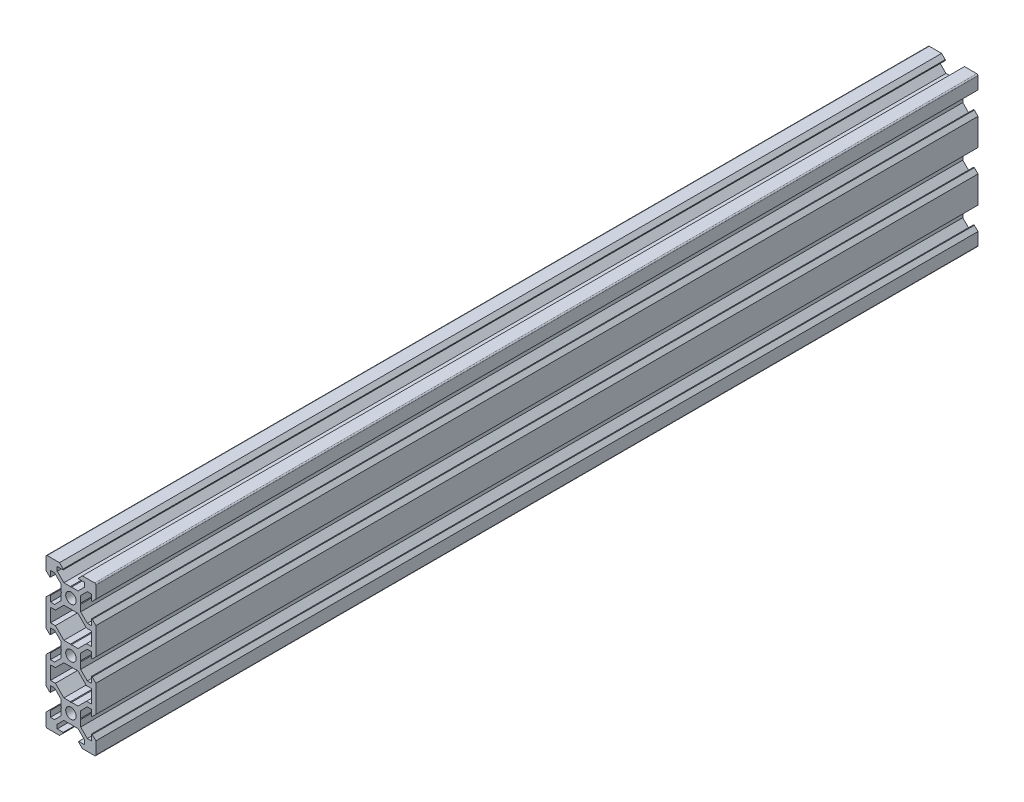
SolidWorks part; units mm, degrees
ref_plane "Plan de face" through (0, 0, 0) normal (0, 0, 1) x (1, 0, 0)
ref_plane "Plan de dessus" through (0, 0, 0) normal (0, 1, 0) x (1, 0, 0)
ref_plane "Plan de droite" through (0, 0, 0) normal (1, 0, 0) x (0, 0, -1)
ref_axis "Axe" through (0, 0, -13.782) along (0, 0, 1)
sketch "Esquisse1" plane through (0, 0, 0) normal (0, 0, 1) x (1, 0, 0)
  line L0 (0, 27.6392) -> (0, -27.6392) construction
  line L1 (-33.6074, 0) -> (33.6074, 0) construction
  line L2 (0, 0) -> (-22.2114, 22.2114) construction
  line L3 (-9.5, 10) -> (-4.58, 10)
  line L4 (-4.58, 10) -> (-3.125, 8.545)
  line L5 (-3.125, 8.545) -> (-3.125, 8.2)
  line L6 (-3.125, 8.2) -> (-5.5, 8.2)
  line L7 (-2.8393, 3.9) -> (-5.5, 6.5607)
  line L8 (-2.8393, 3.9) -> (-0.21, 3.9)
  line L9 (-5.5, 6.5607) -> (-5.5, 8.2)
  line L10 (0, 3.69) -> (0, 2.1)
  line L11 (-3.9, 2.8393) -> (-6.5607, 5.5)
  line L12 (-8.545, 3.125) -> (-8.2, 3.125)
  line L13 (-8.2, 3.125) -> (-8.2, 5.5)
  line L14 (-6.5607, 5.5) -> (-8.2, 5.5)
  line L15 (-10, 4.58) -> (-8.545, 3.125)
  line L16 (-10, 9.5) -> (-10, 4.58)
  line L17 (-0.21, 3.9) -> (0, 3.69)
  line L18 (-3.9, 2.8393) -> (-3.9, 0.21)
  line L19 (-6.2393, -12.7) -> (-8.2, -12.7)
  line L20 (-3.9, 0.21) -> (-3.69, 0)
  line L21 (-0.21, -3.9) -> (0, -3.69)
  line L22 (0, -3.69) -> (0, -2.1)
  line L23 (-6.5607, -5.5) -> (-8.2, -5.5)
  line L24 (-2.8393, -3.9) -> (-0.21, -3.9)
  line L25 (-8.545, -3.125) -> (-8.2, -3.125)
  line L26 (-10, -4.58) -> (-8.545, -3.125)
  line L27 (-8.2, -3.125) -> (-8.2, -5.5)
  line L28 (-2.8393, -3.9) -> (-6.2393, -7.3)
  line L29 (-3.9, -2.8393) -> (-6.5607, -5.5)
  line L30 (-3.9, -2.8393) -> (-3.9, -0.21)
  line L31 (-3.9, -0.21) -> (-3.69, 0)
  line L32 (-6.2393, -7.3) -> (-8.2, -7.3)
  line L33 (-8.2, -7.3) -> (-8.2, -12.7)
  line L34 (-8.2, -10) -> (-10, -10) construction
  line L35 (-10, -15.42) -> (-10, -4.58)
  line L36 (-3.9, -19.79) -> (-3.69, -20)
  line L37 (-3.9, -17.1607) -> (-3.9, -19.79)
  line L38 (-3.9, -17.1607) -> (-6.5607, -14.5)
  line L39 (-2.8393, -16.1) -> (-6.2393, -12.7)
  line L40 (-8.2, -16.875) -> (-8.2, -14.5)
  line L41 (-10, -15.42) -> (-8.545, -16.875)
  line L42 (-8.545, -16.875) -> (-8.2, -16.875)
  line L43 (-2.8393, -16.1) -> (-0.21, -16.1)
  line L44 (-6.5607, -14.5) -> (-8.2, -14.5)
  line L45 (0, -16.31) -> (0, -17.9)
  line L46 (-0.21, -16.1) -> (0, -16.31)
  line L47 (-8.2, -30) -> (-10, -30) construction
  line L48 (-3.69, -20) -> (0, -20) construction
  line L49 (-0.21, -23.9) -> (0, -23.69)
  line L50 (0, -23.69) -> (0, -22.1)
  line L51 (-6.5607, -25.5) -> (-8.2, -25.5)
  line L52 (-2.8393, -23.9) -> (-0.21, -23.9)
  line L53 (-8.545, -23.125) -> (-8.2, -23.125)
  line L54 (-10, -24.58) -> (-8.545, -23.125)
  line L55 (-8.2, -23.125) -> (-8.2, -25.5)
  line L56 (-2.8393, -23.9) -> (-6.2393, -27.3)
  line L57 (-3.9, -22.8393) -> (-6.5607, -25.5)
  line L58 (-3.9, -22.8393) -> (-3.9, -20.21)
  line L59 (-3.9, -20.21) -> (-3.69, -20)
  line L60 (-10, -24.58) -> (-10, -35.42)
  line L61 (-8.2, -32.7) -> (-8.2, -27.3)
  line L62 (-6.2393, -32.7) -> (-8.2, -32.7)
  line L63 (-3.9, -39.79) -> (-3.69, -40)
  line L64 (-3.9, -37.1607) -> (-3.9, -39.79)
  line L65 (-3.9, -37.1607) -> (-6.5607, -34.5)
  line L66 (-2.8393, -36.1) -> (-6.2393, -32.7)
  line L67 (-8.2, -36.875) -> (-8.2, -34.5)
  line L68 (-10, -35.42) -> (-8.545, -36.875)
  line L69 (-8.545, -36.875) -> (-8.2, -36.875)
  line L70 (-2.8393, -36.1) -> (-0.21, -36.1)
  line L71 (-6.5607, -34.5) -> (-8.2, -34.5)
  line L72 (0, -36.31) -> (0, -37.9)
  line L73 (-0.21, -36.1) -> (0, -36.31)
  line L74 (-3.9, -40.21) -> (-3.69, -40)
  line L75 (-6.2393, -27.3) -> (-8.2, -27.3)
  line L76 (-3.9, -42.8393) -> (-3.9, -40.21)
  line L77 (-0.21, -43.9) -> (0, -43.69)
  line L78 (-10, -49.5) -> (-10, -44.58)
  line L79 (-10, -44.58) -> (-8.545, -43.125)
  line L80 (-6.5607, -45.5) -> (-8.2, -45.5)
  line L81 (-8.2, -43.125) -> (-8.2, -45.5)
  line L82 (-8.545, -43.125) -> (-8.2, -43.125)
  line L83 (-3.9, -42.8393) -> (-6.5607, -45.5)
  line L84 (0, -43.69) -> (0, -42.1)
  line L85 (-5.5, -46.5607) -> (-5.5, -48.2)
  line L86 (-2.8393, -43.9) -> (-0.21, -43.9)
  line L87 (-2.8393, -43.9) -> (-5.5, -46.5607)
  line L88 (-3.125, -48.2) -> (-5.5, -48.2)
  line L89 (-3.125, -48.545) -> (-3.125, -48.2)
  line L90 (-4.58, -50) -> (-3.125, -48.545)
  line L91 (-9.5, -50) -> (-4.58, -50)
  arc A0 (0, -2.1) -> (0, 2.1) centre (0, 0) cw
  arc A1 (-9.5, 10) -> (-10, 9.5) centre (-9.5, 9.5) ccw
  arc A2 (0, -37.9) -> (0, -42.1) centre (0, -40) ccw
  arc A3 (-9.5, -50) -> (-10, -49.5) centre (-9.5, -49.5) cw
  arc A4 (0, -17.9) -> (0, -22.1) centre (0, -20) ccw
  point P4 (0, 0)
  point P7 (0, 0)
  point P30 (-10, 10)
  point P60 (0, -20)
  point P111 (-10, -50)
  dimension "D5" = 11
  dimension "D2" = 2.1
  dimension "D3" = 6.25
  dimension "D10" = 0.5
  dimension "D4" = 9.16
  dimension "D6" = 1.5
  dimension "D7" = 1.8
  dimension "D8" = 4.3
  dimension "D9" = 20
  dimension "D11" = 0.42
  dimension "D12" = 10
  dimension "D13" = 1.8
extrude "Boss.-Extru.1" add sketch "Esquisse1" along normal blind 353.7
sketch "Esquisse3" plane through (0, 0, 353.7) normal (0, 0, 1) x (1, 0, 0)
  line L0 (0, 0) -> (-9.8536, 9.8536) construction
  line L1 (-8.2, 8.2) -> (-8.2, 6.57)
  line L2 (-8.2, 6.57) -> (-7.54, 6.57)
  line L3 (-7.54, 6.57) -> (-6.57, 7.54)
  line L4 (-8.2, 3.125) -> (-8.2, 5.5) construction
  line L5 (-6.57, 8.2) -> (-6.57, 7.54)
  line L6 (-8.2, 8.2) -> (-6.57, 8.2)
  line L7 (-5.5, 6.5607) -> (-5.5, 8.2) construction
  line L8 (-3.69, -20) -> (0, -20) construction
  line L9 (-8.2, -48.2) -> (-6.57, -48.2)
  line L10 (-6.57, -48.2) -> (-6.57, -47.54)
  line L11 (-7.54, -46.57) -> (-6.57, -47.54)
  line L12 (-8.2, -46.57) -> (-7.54, -46.57)
  line L13 (-8.2, -48.2) -> (-8.2, -46.57)
  arc A0 (-9.5, 10) -> (-10, 9.5) centre (-9.5, 9.5) ccw construction
  point P13 (-7.055, 7.055)
  point P14 (-6.57, 7.87)
  point P26 (-7.055, -47.055)
  dimension "D1" = 1.07
extrude "Enlèv. mat.-Extru.1" [suppressed] cut sketch "Esquisse3" against normal through all
mirror "Symétrie1" about plane through (0, 3.69, 353.7) normal (-1, 0, 0) of "Enlèv. mat.-Extru.1", "Boss.-Extru.1"
